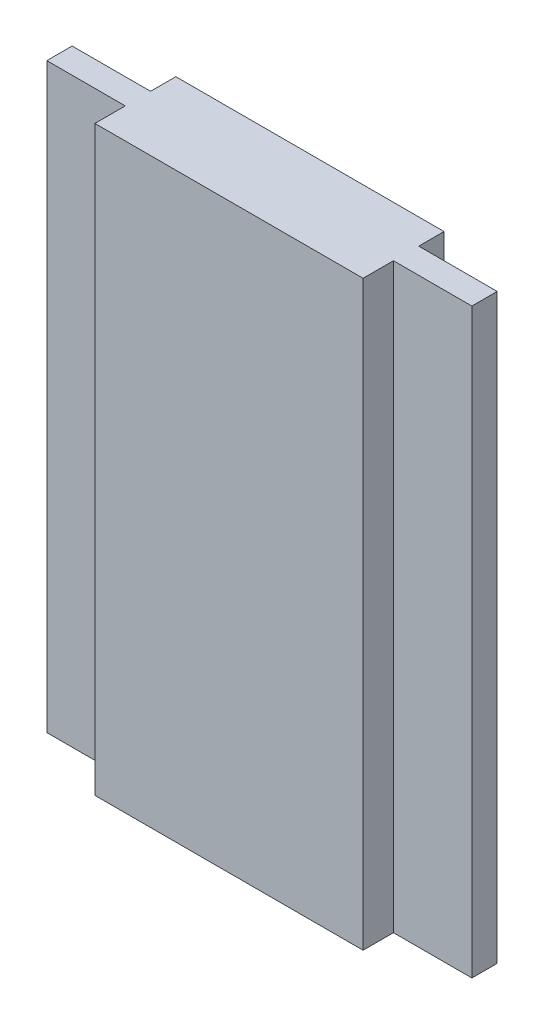
SolidWorks part; units mm, degrees
ref_plane "Front" through (0, 0, 0) normal (0, 0, 1) x (1, 0, 0)
ref_plane "Top" through (0, 0, 0) normal (0, 1, 0) x (1, 0, 0)
ref_plane "Right" through (0, 0, 0) normal (1, 0, 0) x (0, 0, -1)
sketch "Sketch2" plane through (0, 0, 0) normal (0, 0, 1) x (1, 0, 0)
  line L1 (0, 0) -> (84, 0)
  line L2 (0, 0) -> (0, 115)
  line L3 (0, 115) -> (84, 115)
  line L4 (84, 0) -> (84, 115)
  dimension "D1" = 84
  dimension "D2" = 115
extrude "Boss-Extrude1" add sketch "Sketch2" along normal blind 15
sketch "Sketch3" plane through (0, 115, 0) normal (0, 1, 0) x (1, 0, 0)
  line L1 (0, -15) -> (15.5, -15)
  line L2 (0, -15) -> (0, -10)
  line L3 (0, -10) -> (15.5, -10)
  line L4 (15.5, -15) -> (15.5, -10)
  dimension "D1" = 15.5
  dimension "D2" = 5
ref_plane "Plane1" through (0, 0, 7.5) normal (0, 0, 1) x (1, 0, 0)
ref_plane "Plane2" through (42, 0, 0) normal (-1, 0, 0) x (0, 0, 1)
ref_axis "Axis1" through (42, 120.75, 7.5) along (0, -1, 0)
extrude "Cut-Extrude1" cut sketch "Sketch3" against normal through all
mirror "Mirror1" about plane through (0, 0, 7.5) normal (0, 0, 1) of "Cut-Extrude1"
mirror "Mirror2" about plane through (42, 0, 0) normal (-1, 0, 0) of "Mirror1"
sketch "Sketch4" plane through (0, 0, 15) normal (0, 0, 1) x (1, 0, 0)
  line L1 (15.5, 115) -> (68.5, 115)
  line L2 (15.5, 115) -> (15.5, 0)
  line L3 (15.5, 0) -> (68.5, 0)
  line L4 (68.5, 115) -> (68.5, 0)
extrude "Boss-Extrude2" add sketch "Sketch4" along normal blind 1
